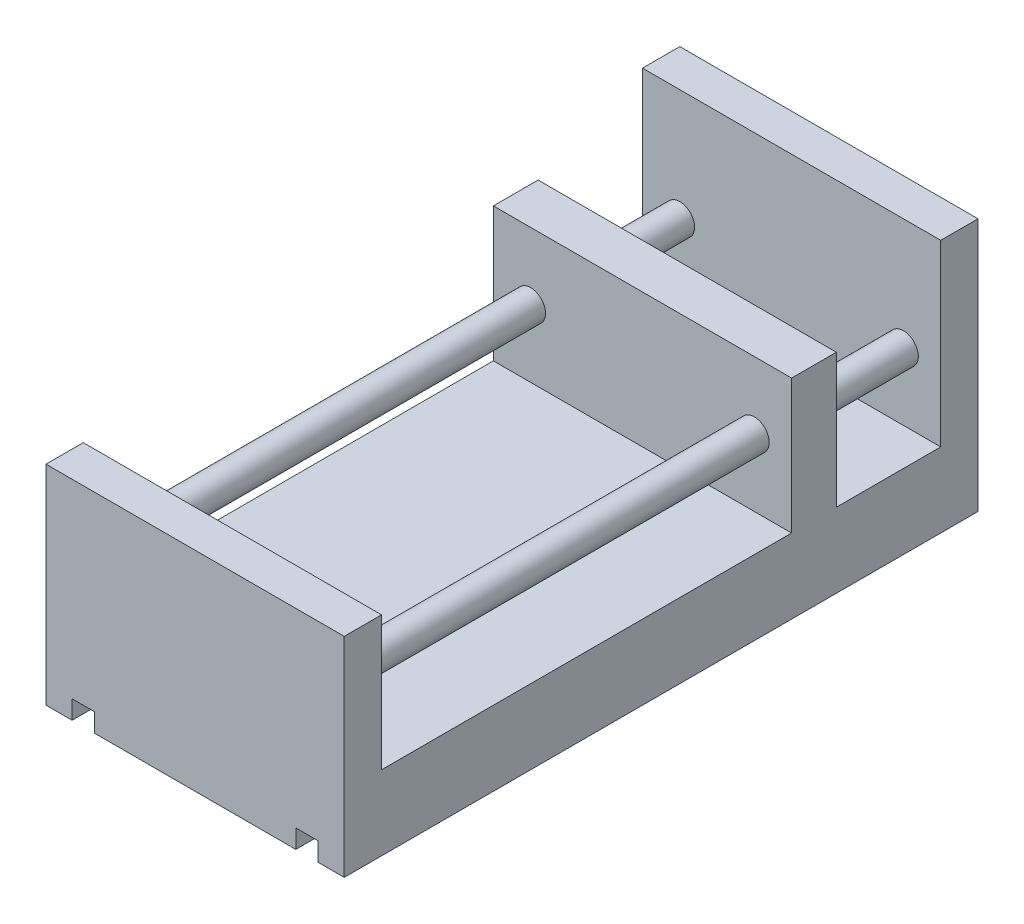
SolidWorks part; units mm, degrees
ref_plane "Front Plane" through (0, 0, 0) normal (0, 0, 1) x (1, 0, 0)
ref_plane "Top Plane" through (0, 0, 0) normal (0, 1, 0) x (1, 0, 0)
ref_plane "Right Plane" through (0, 0, 0) normal (1, 0, 0) x (0, 0, -1)
sketch "Sketch1" plane through (0, 0, 0) normal (0, 1, 0) x (1, 0, 0)
  line L1 (-40, 85) -> (40, 85)
  line L2 (-40, 85) -> (-40, -85)
  line L3 (-40, -85) -> (40, -85)
  line L4 (40, 85) -> (40, -85)
  line L5 (-40, 85) -> (40, -85) construction
  line L6 (-40, -85) -> (40, 85) construction
  line L7 (-40, 85) -> (40, 85)
  line L8 (-40, 85) -> (-40, 75)
  line L9 (-40, 75) -> (40, 75)
  line L10 (40, 85) -> (40, 75)
  line L11 (-40, -75) -> (40, -75)
  line L12 (-40, -75) -> (-40, -85)
  line L13 (-40, -85) -> (40, -85)
  line L14 (40, -75) -> (40, -85)
  line L15 (-40, 47) -> (40, 47)
  line L16 (-40, 47) -> (-40, 35)
  line L17 (-40, 35) -> (40, 35)
  line L18 (40, 47) -> (40, 35)
  point P0 (0, 0)
  dimension "D1" = 80
  dimension "D2" = 170
  dimension "D3" = 10
  dimension "D4" = 10
  dimension "D5" = 12
  dimension "D6" = 28
extrude "Boss-Extrude1" add sketch "Sketch1" along normal blind 20 contours L17 L2 L11 L4 | L2 L15 L4 L9 region at (0, 0, -61) region at (0, 0, 20)
extrude "Boss-Extrude2" add sketch "Sketch1<3>" along normal blind 56 contours L11 L2 L3 L4 | L2 L17 L4 L15 region at (0, 0, -41) region at (0, 0, 80)
sketch "Sketch1<3>" plane through (0, 0, 0) normal (0, 1, 0) x (1, 0, 0) same geometry as "Sketch1"
extrude "Boss-Extrude3" add sketch "Sketch1<4>" along normal blind 68 contours L2 L9 L4 L1 region at (0, 0, -80)
sketch "Sketch1<4>" plane through (0, 0, 0) normal (0, 1, 0) x (1, 0, 0) same geometry as "Sketch1"
sketch "Sketch2" plane through (0, 0, 75) normal (0, 0, -1) x (-1, 0, 0)
  line L0 (-40, 38) -> (40, 38) construction
  line L1 (-40, 56) -> (-40, 20) construction
  line L2 (40, 56) -> (40, 20) construction
  line L3 (0, 56) -> (0, 20) construction
  line L4 (40, 56) -> (-40, 56) construction
  line L5 (40, 20) -> (-40, 20) construction
  circle A0 centre (-30, 38) radius 4
  circle A1 centre (30, 38) radius 4
  point P12 (0, 38)
  dimension "D1" = 8
  dimension "D2" = 8
  dimension "D3" = 60
  dimension "D4" = 30
extrude "Boss-Extrude4" add sketch "Sketch2" along normal blind 150
sketch "Sketch3" plane through (0, 0, 0) normal (0, -1, 0) x (1, 0, 0)
  line L0 (-33, 85) -> (-33, -85)
  line L1 (-40, 85) -> (40, 85) construction
  line L2 (-40, -85) -> (40, -85) construction
  line L3 (33, 85) -> (33, -85)
  line L4 (-27, 85) -> (-27, -85)
  line L5 (27, 85) -> (27, -85)
  line L6 (-33, 85) -> (-27, 85)
  line L7 (27, 85) -> (33, 85)
  line L8 (33, -85) -> (27, -85)
  line L9 (-27, -85) -> (-33, -85)
  dimension "D1" = 66
  dimension "D2" = 33
  dimension "D3" = 54
  dimension "D4" = 27
extrude "Cut-Extrude1" cut sketch "Sketch3" against normal blind 5
